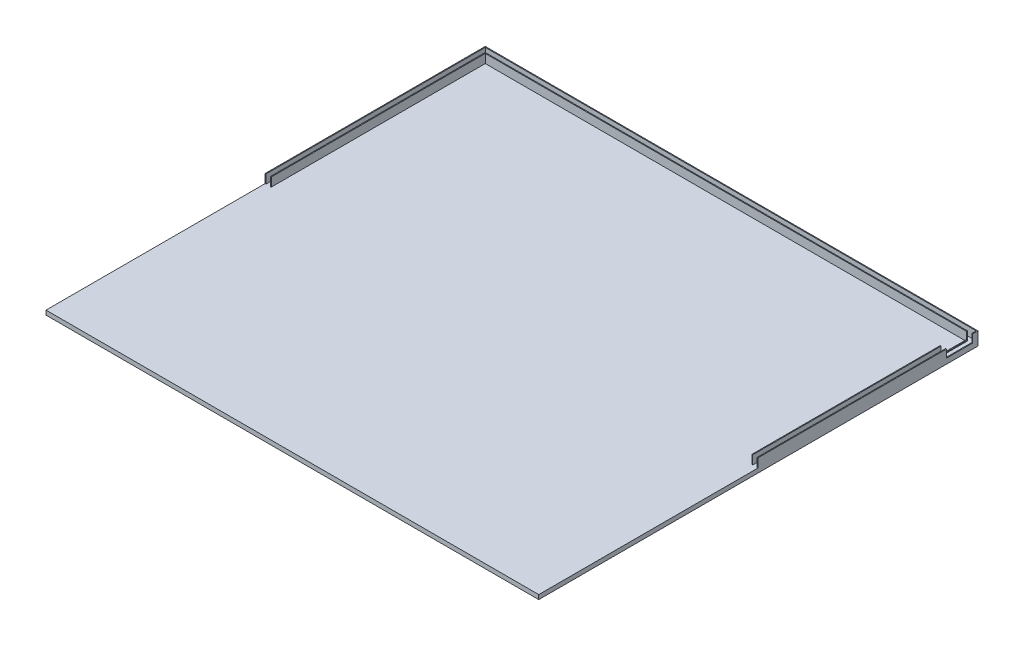
SolidWorks part; units mm, degrees
ref_plane "Plano frontal" through (0, 0, 0) normal (0, 0, 1) x (1, 0, 0)
ref_plane "Plano superior" through (0, 0, 0) normal (0, 1, 0) x (1, 0, 0)
ref_plane "Plano direito" through (0, 0, 0) normal (1, 0, 0) x (0, 0, -1)
sketch "Esboço1" plane through (0, 0, 0) normal (0, 1, 0) x (1, 0, 0)
  line L1 (-97.6046, 71.0856) -> (464.3954, 71.0856)
  line L2 (-97.6046, 71.0856) -> (-97.6046, -429.9144)
  line L3 (-97.6046, -429.9144) -> (464.3954, -429.9144)
  line L4 (464.3954, 71.0856) -> (464.3954, -429.9144)
  line L5 (-97.6046, 71.0856) -> (464.3954, -429.9144) construction
  line L6 (-97.6046, -429.9144) -> (464.3954, 71.0856) construction
  point P0 (183.3954, -179.4144)
  dimension "D1" = 562
  dimension "D2" = 501
extrude "Ressalto-extrusão1" add sketch "Esboço1" along normal blind 5
sketch "Esboço2" plane through (0, 5, 0) normal (0, 1, 0) x (1, 0, 0)
  line L1 (-97.6046, 71.0856) -> (-90.6046, 71.0856)
  line L2 (-97.6046, 71.0856) -> (-97.6046, -179.9144)
  line L3 (-97.6046, -179.9144) -> (-90.6046, -179.9144)
  line L4 (-90.6046, 71.0856) -> (-90.6046, -179.9144)
  dimension "D1" = 7
  dimension "D2" = 251
extrude "Ressalto-extrusão2" add sketch "Esboço2" along normal blind 10
sketch "Esboço6" plane through (0, 5, 0) normal (0, 1, 0) x (1, 0, 0)
  line L1 (464.3954, 71.0856) -> (457.3954, 71.0856)
  line L2 (464.3954, 71.0856) -> (464.3954, -179.9144)
  line L3 (464.3954, -179.9144) -> (457.3954, -179.9144)
  line L4 (457.3954, 71.0856) -> (457.3954, -179.9144)
  dimension "D1" = 7
  dimension "D2" = 251
extrude "Ressalto-extrusão3" add sketch "Esboço6" along normal blind 10
sketch "Esboço7" plane through (0, 15, 0) normal (0, 1, 0) x (1, 0, 0)
  line L0 (-97.6046, 71.0856) -> (-97.6046, -179.9144) construction
  line L1 (-96.6046, 71.0856) -> (-91.6046, 71.0856)
  line L2 (-96.6046, 71.0856) -> (-96.6046, -179.9144)
  line L3 (-96.6046, -179.9144) -> (-91.6046, -179.9144)
  line L4 (-91.6046, 71.0856) -> (-91.6046, -179.9144)
  line L5 (-96.6046, 71.0856) -> (-91.6046, -179.9144) construction
  line L6 (-96.6046, -179.9144) -> (-91.6046, 71.0856) construction
  line L7 (-90.6046, -179.9144) -> (-90.6046, 71.0856) construction
  line L8 (-97.6046, -179.9144) -> (-90.6046, -179.9144) construction
  line L9 (-90.6046, 71.0856) -> (-97.6046, 71.0856) construction
  point P0 (-94.1046, -54.4144)
  dimension "D1" = 1
  dimension "D2" = 1
  dimension "D3" = 0
  dimension "D4" = 0
extrude "Corte-extrusão1" cut sketch "Esboço7" against normal blind 10
sketch "Esboço9" plane through (0, 15, 0) normal (0, 1, 0) x (1, 0, 0)
  line L0 (464.3954, -179.9144) -> (464.3954, 71.0856) construction
  line L1 (458.3954, 71.0856) -> (463.3954, 71.0856)
  line L2 (458.3954, 71.0856) -> (458.3954, -179.9144)
  line L3 (458.3954, -179.9144) -> (463.3954, -179.9144)
  line L4 (463.3954, 71.0856) -> (463.3954, -179.9144)
  line L5 (458.3954, 71.0856) -> (463.3954, -179.9144) construction
  line L6 (458.3954, -179.9144) -> (463.3954, 71.0856) construction
  line L7 (457.3954, 71.0856) -> (457.3954, -179.9144) construction
  line L9 (457.3954, -179.9144) -> (464.3954, -179.9144) construction
  line L10 (464.3954, 71.0856) -> (457.3954, 71.0856) construction
  point P0 (460.8954, -54.4144)
  dimension "D1" = 1
  dimension "D2" = 1
  dimension "D3" = 0
  dimension "D4" = 0
extrude "Corte-extrusão3" cut sketch "Esboço9" against normal blind 10
sketch "Esboço10" plane through (0, 5, 0) normal (0, 1, 0) x (1, 0, 0)
  line L0 (464.3954, -179.9144) -> (464.3954, 71.0856) construction
  line L1 (-97.6046, 71.0856) -> (464.3954, 71.0856)
  line L2 (-97.6046, 71.0856) -> (-97.6046, 64.0856)
  line L3 (-97.6046, 64.0856) -> (464.3954, 64.0856)
  line L4 (464.3954, 71.0856) -> (464.3954, 64.0856)
  dimension "D1" = 7
extrude "Ressalto-extrusão4" add sketch "Esboço10" along normal blind 10
sketch "Esboço15" plane through (0, 15, 0) normal (0, 1, 0) x (1, 0, 0)
  line L0 (464.3954, 71.0856) -> (-97.6046, 71.0856) construction
  line L1 (-96.6046, 70.0856) -> (463.3954, 70.0856)
  line L2 (-96.6046, 70.0856) -> (-96.6046, 65.0856)
  line L3 (-96.6046, 65.0856) -> (463.3954, 65.0856)
  line L4 (463.3954, 70.0856) -> (463.3954, 65.0856)
  line L5 (-96.6046, 70.0856) -> (463.3954, 65.0856) construction
  line L6 (-96.6046, 65.0856) -> (463.3954, 70.0856) construction
  line L7 (-90.6046, 64.0856) -> (457.3954, 64.0856) construction
  line L8 (464.3954, -179.9144) -> (464.3954, 71.0856) construction
  line L9 (-97.6046, 71.0856) -> (-97.6046, -179.9144) construction
  point P0 (183.3954, 67.5856)
  dimension "D1" = 1
  dimension "D2" = 1
  dimension "D3" = 1
  dimension "D4" = 1
extrude "Corte-extrusão11" cut sketch "Esboço15" against normal blind 10
sketch "Esboço16" plane through (0, 15, 0) normal (0, 1, 0) x (1, 0, 0)
  line L1 (458.3954, 64.0856) -> (463.3954, 64.0856)
  line L2 (458.3954, 64.0856) -> (458.3954, 65.0856)
  line L3 (458.3954, 65.0856) -> (463.3954, 65.0856)
  line L4 (463.3954, 64.0856) -> (463.3954, 65.0856)
  line L5 (-96.6046, 65.0856) -> (-91.6046, 65.0856)
  line L6 (-96.6046, 65.0856) -> (-96.6046, 64.0856)
  line L7 (-96.6046, 64.0856) -> (-91.6046, 64.0856)
  line L8 (-91.6046, 65.0856) -> (-91.6046, 64.0856)
extrude "Corte-extrusão12" cut sketch "Esboço16" against normal blind 10
sketch "Esboço20" plane through (0, 0, 0) normal (0, -1, 0) x (1, 0, 0)
  line L0 (-97.6046, 429.9144) -> (464.3954, 429.9144) construction
  line L1 (-97.6046, -71.0856) -> (-97.6046, 429.9144) construction
  line L2 (464.3954, -71.0856) -> (-97.6046, -71.0856) construction
  line L3 (464.3954, 429.9144) -> (464.3954, -71.0856) construction
  circle A0 centre (-47.6046, 379.9144) radius 15
  circle A1 centre (414.3954, 379.9144) radius 15
  circle A2 centre (414.3954, -21.0856) radius 15
  circle A3 centre (-47.6046, -21.0856) radius 15
  dimension "D1" = 50
  dimension "D2" = 50
  dimension "D3" = 50
  dimension "D4" = 50
  dimension "D5" = 50
  dimension "D6" = 50
  dimension "D7" = 50
  dimension "D8" = 50
extrude "Ressalto-extrusão5" add sketch "Esboço20" along normal blind 10
sketch "Esboço21" plane through (0, 15, 0) normal (0, 1, 0) x (1, 0, 0)
  line L0 (458.3954, 65.0856) -> (458.3954, -179.9144) construction
  line L1 (457.3954, 64.0856) -> (458.3954, 64.0856)
  line L2 (457.3954, 64.0856) -> (457.3954, 35.0856)
  line L3 (457.3954, 35.0856) -> (458.3954, 35.0856)
  line L4 (458.3954, 64.0856) -> (458.3954, 35.0856)
  line L5 (463.3954, -179.9144) -> (463.3954, 70.0856) construction
  line L6 (463.3954, 35.0856) -> (464.3954, 35.0856)
  line L7 (463.3954, 35.0856) -> (463.3954, 65.0856)
  line L8 (463.3954, 65.0856) -> (464.3954, 65.0856)
  line L9 (464.3954, 35.0856) -> (464.3954, 65.0856)
  line L10 (464.3954, -179.9144) -> (464.3954, 71.0856) construction
  dimension "D1" = 29
  dimension "D2" = 30
extrude "Corte-extrusão13" cut sketch "Esboço21" against normal blind 9
